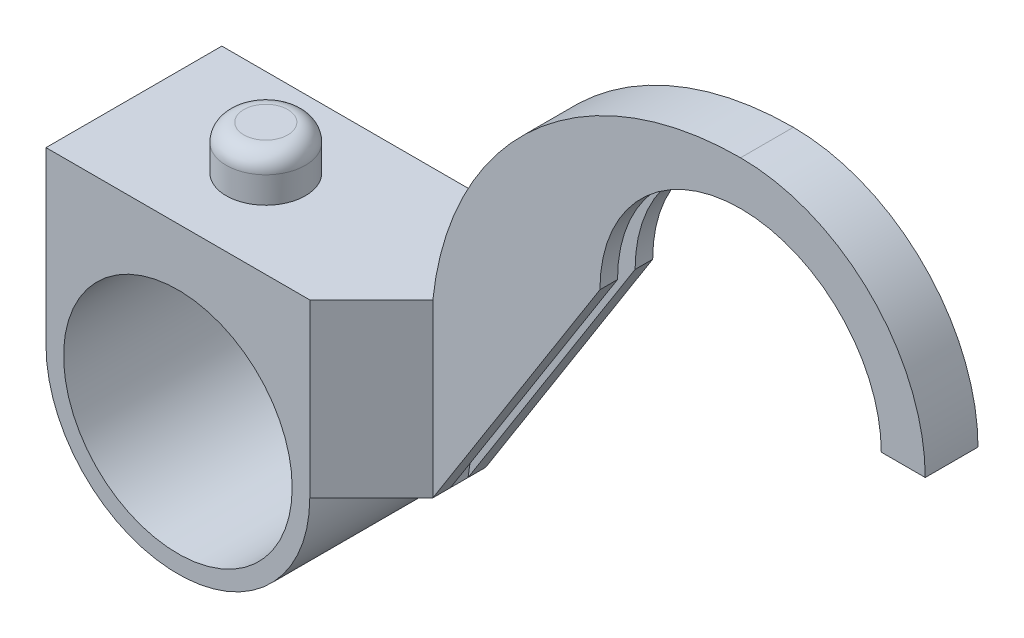
SolidWorks part; units mm, degrees
ref_plane "Front Plane" through (0, 0, 0) normal (0, 0, 1) x (1, 0, 0)
ref_plane "Top Plane" through (0, 0, 0) normal (0, 1, 0) x (1, 0, 0)
ref_plane "Right Plane" through (0, 0, 0) normal (1, 0, 0) x (0, 0, -1)
sketch "Sketch1" plane through (0, 0, 0) normal (0, 0, 1) x (1, 0, 0)
  line L0 (-15, 0) -> (-15, 19.5)
  line L1 (-15, 19.5) -> (15, 19.5)
  line L2 (15, 19.5) -> (15, 0)
  circle A0 centre (0, 0) radius 13
  arc A1 (-15, 0) -> (15, 0) centre (0, 0) ccw
  circle A2 centre (0, 0) radius 15 construction
  dimension "D1" = 26
  dimension "D2" = 2
  dimension "D3" = 19.5
extrude "Boss-Extrude1" add sketch "Sketch1" along normal mid plane 20
sketch "Sketch3" plane through (0, 19.5, 0) normal (0, 1, 0) x (1, 0, 0)
  line L0 (15, 10) -> (22, 3)
  line L1 (22, 3) -> (22, -3)
  line L2 (22, -3) -> (15, -10)
  line L3 (15, -10) -> (15, 10) construction
  line L4 (15, 10) -> (15, -10)
  dimension "D1" = 6
  dimension "D2" = 7
extrude "Boss-Extrude2" add sketch "Sketch3" against normal up to vertex (19.5 mm away) up to point (15, 0, 10)
sketch "Sketch2" plane through (0, 0, 0) normal (0, 0, 1) x (1, 0, 0)
  line L0 (78, 30) -> (76, 30)
  line L1 (15, 30) -> (15, 0) construction
  line L2 (22, 19.5) -> (22, 0)
  line L3 (15, 30) -> (57, 30) construction
  line L4 (22, 0) -> (22, 19.5) construction
  arc A1 (43.8839, 43.7466) -> (76, 30) centre (57, 30) cw
  arc A2 (57, 51) -> (78, 30) centre (57, 30) cw
  arc A3 (22, 19.5) -> (57, 51) centre (57, 15.8056) cw
  arc A4 (43.8839, 43.7466) -> (22, 0) centre (93.8029, -8.572) ccw
  arc A5 (38, 30) -> (76, 30) centre (57, 30) cw construction
  arc A6 (36, 30) -> (78, 30) centre (57, 30) cw construction
  dimension "D3" = 19
  dimension "D4" = 2
  dimension "D5" = 72.3128
  dimension "D1" = 30
  dimension "D2" = 57
extrude "Boss-Extrude3" add sketch "Sketch2" along normal mid plane 6
sketch "Sketch4" plane through (0, 0, 3) normal (0, 0, 1) x (1, 0, 0)
  line L1 (73, 30) -> (76, 30)
  line L2 (41, 30) -> (22, 0)
  arc A0 (73, 30) -> (41, 30) centre (57, 30) ccw
  arc A1 (76, 30) -> (43.8839, 43.7466) centre (57, 30) ccw
  arc A2 (43.8839, 43.7466) -> (22, 0) centre (93.8029, -8.572) ccw construction
  arc A3 (76, 30) -> (43.8839, 43.7466) centre (57, 30) ccw construction
  arc A4 (22, 0) -> (43.8839, 43.7466) centre (93.8029, -8.572) cw
  dimension "D1" = 16
  dimension "D2" = 19
  dimension "D4" = 19
  dimension "D3" = 3
extrude "Boss-Extrude4" add sketch "Sketch4" against normal blind 2 separate body
mirror "Mirror1" about plane through (0, 0, 0) normal (0, 0, 1) of bodies 104
combine bodies "Combine2" operation type add bodies to combine 104 105 103
sketch "Sketch5" plane through (0, 19.5, 0) normal (0, 1, 0) x (1, 0, 0)
  circle A0 centre (0, 0) radius 4.5
  dimension "D1" = 9
extrude "Boss-Extrude5" add sketch "Sketch5" along normal mid plane 10 contours A0
fillet "Fillet1" radius 2 1 edges at (0, 24.5, 4.5)
